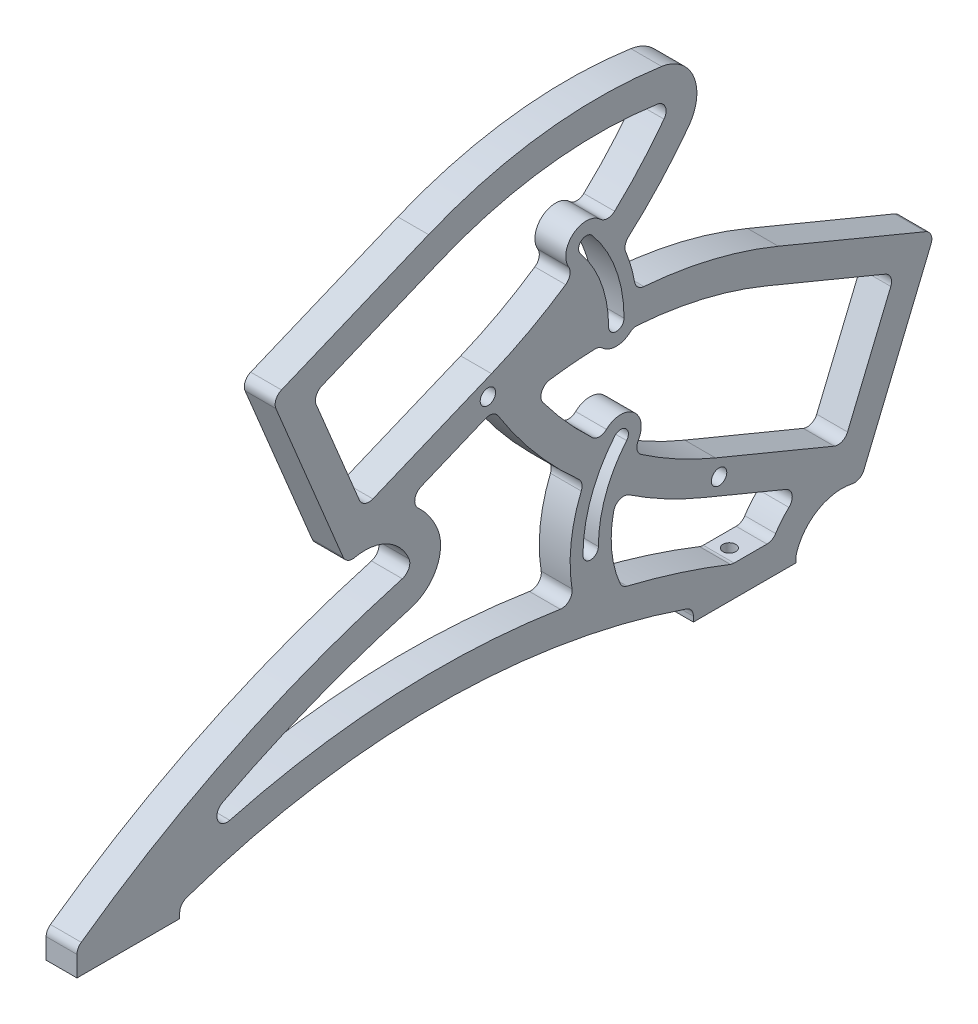
SolidWorks part; units mm, degrees
material "1060 Alloy"
ref_plane "Front Plane" through (0, 0, 0) normal (0, 0, 1) x (1, 0, 0)
ref_plane "Top Plane" through (0, 0, 0) normal (0, 1, 0) x (1, 0, 0)
ref_plane "Right Plane" through (0, 0, 0) normal (1, 0, 0) x (0, 0, -1)
sketch "Sketch1" plane through (0, 0, 0) normal (1, 0, 0) x (0, 0, -1)
  line L0 (0, 0) -> (0, 5)
  line L1 (38.8897, 78.8553) -> (54.5797, 40.9762) construction
  line L2 (38.8897, 78.8553) -> (112.8001, 109.47) construction
  line L3 (54.5797, 40.9762) -> (128.4901, 71.5909) construction
  line L4 (41.8855, 76.849) -> (54.1314, 47.2849) construction
  line L5 (112.8001, 109.47) -> (128.4901, 71.5909) construction
  line L6 (20, 1) -> (20, 0)
  line L7 (0, 0) -> (20, 0)
  line L8 (54.1314, 47.2849) -> (81.8478, 58.7654) construction
  line L9 (69.6019, 88.3295) -> (41.8855, 76.849) construction
  line L10 (80, 58) -> (105, 58) construction
  line L11 (99.1511, 74.0697) -> (80, 58) construction
  line L12 (100, 22) -> (125, 22) construction
  line L13 (125, 22) -> (105.8489, 38.0697) construction
  line L14 (166.1103, 42.8553) -> (150.4203, 4.9762) construction
  line L15 (166.1103, 42.8553) -> (92.1999, 73.47) construction
  line L16 (150.4203, 4.9762) -> (76.5099, 35.5909) construction
  line L17 (92.1999, 73.47) -> (76.5099, 35.5909) construction
  line L18 (150.8686, 11.2849) -> (163.1145, 40.849) construction
  line L19 (163.1145, 40.849) -> (135.3981, 52.3295) construction
  line L20 (123.1522, 22.7654) -> (150.8686, 11.2849) construction
  line L21 (156.9916, 26.0669) -> (84.929, 55.9162) construction
  line L22 (48.0084, 62.0669) -> (120.071, 91.9162) construction
  line L23 (152.4922, 7.3652) -> (167.0342, 42.4726)
  line L24 (167.0342, 42.4726) -> (136.5462, 55.1012)
  line L25 (68.4538, 91.1012) -> (37.9658, 78.4726)
  line L26 (37.9658, 78.4726) -> (52.5078, 43.3652)
  line L27 (63.7245, 48.0113) -> (81.1111, 55.2131)
  line L28 (140, 0) -> (140, 1)
  line L29 (152.4922, 7.3652) -> (143.6238, 11.0386) construction
  line L30 (80.6997, 61.537) -> (55.755, 51.2046)
  line L31 (55.755, 51.2046) -> (45.8052, 75.2254)
  line L32 (45.8052, 75.2254) -> (70.7499, 85.5579)
  line L33 (124.3003, 25.537) -> (149.245, 15.2046)
  line L34 (149.245, 15.2046) -> (159.1948, 39.2254)
  line L35 (159.1948, 39.2254) -> (134.2501, 49.5579)
  line L36 (56.0604, 34.7884) -> (62.7895, 37.5756) construction
  line L37 (52.5078, 43.3652) -> (58.8317, 45.9846) construction
  line L38 (122.0042, 19.9937) -> (141.2755, 12.0113)
  line L39 (135.4645, 6) -> (127.5413, 6)
  line L43 (140, 0) -> (120, 0)
  line L56 (120, 1) -> (120, 0)
  line L63 (174.6584, 98) -> (-14.1241, 98) construction
  circle A0 centre (80, 58) radius 1.5
  circle A1 centre (125, 22) radius 1.5
  arc A2 (99.1511, 74.0697) -> (105, 58) centre (80, 58) cw construction
  arc A3 (106.5, 58) -> (100.3002, 75.0339) centre (80, 58) ccw
  arc A4 (103.5, 58) -> (98.002, 73.1055) centre (80, 58) ccw
  arc A5 (103.5, 58) -> (106.5, 58) centre (105, 58) ccw
  arc A6 (100.3002, 75.0339) -> (98.002, 73.1055) centre (99.1511, 74.0697) ccw
  arc A7 (105.8489, 38.0697) -> (100, 22) centre (125, 22) ccw construction
  arc A8 (104.6998, 39.0339) -> (98.5, 22) centre (125, 22) ccw
  arc A9 (106.998, 37.1055) -> (101.5, 22) centre (125, 22) ccw
  arc A10 (106.998, 37.1055) -> (104.6998, 39.0339) centre (105.8489, 38.0697) ccw
  arc A11 (98.5, 22) -> (101.5, 22) centre (100, 22) ccw
  arc A12 (81.8478, 58.7654) -> (116.6864, 85.8633) centre (49.9981, 135.6573) ccw construction
  arc A13 (116.6864, 85.8633) -> (113.3977, 93.803) centre (112.68, 88.8548) ccw construction
  arc A14 (113.3977, 93.803) -> (69.6019, 88.3295) centre (101.4516, 11.4375) ccw construction
  arc A15 (135.3981, 52.3295) -> (91.6023, 57.803) centre (103.5484, -24.5625) ccw construction
  arc A16 (91.6023, 57.803) -> (88.3136, 49.8633) centre (92.32, 52.8548) ccw construction
  arc A17 (88.3136, 49.8633) -> (123.1522, 22.7654) centre (155.0019, 99.6573) ccw construction
  arc A18 (106.2569, 70.3115) -> (108.7873, 61.5055) centre (80, 58) cw
  arc A19 (106.2569, 70.3115) -> (119.0902, 84.0685) centre (49.9981, 135.6573) ccw
  arc A20 (119.0902, 84.0685) -> (113.8283, 96.7719) centre (112.68, 88.8548) ccw
  arc A21 (113.8283, 96.7719) -> (68.4538, 91.1012) centre (101.4516, 11.4375) ccw
  arc A23 (81.1111, 55.2131) -> (98.7431, 34.3115) centre (155.0019, 99.6573) ccw
  arc A24 (152.4922, 7.3652) -> (140.0944, 1.6073) centre (148.9396, -1.2116) ccw
  arc A25 (140.0944, 1.6073) -> (140, 1) centre (142, 1) ccw
  arc A26 (20, 1) -> (21.3514, 2.8919) centre (22, 1) cw
  arc A27 (52.5078, 43.3652) -> (64.6372, 38.341) centre (56.0604, 34.7884) cw
  arc A28 (70.7499, 85.5579) -> (112.9671, 90.8341) centre (101.4516, 11.4375) cw
  arc A29 (112.9671, 90.8341) -> (114.2826, 87.6582) centre (112.68, 88.8548) cw
  arc A30 (114.2826, 87.6582) -> (103.1061, 75.5245) centre (49.9981, 135.6573) cw
  arc A31 (103.1061, 75.5245) -> (102.2153, 76.6408) centre (80, 58) ccw
  arc A32 (102.2153, 76.6408) -> (96.0869, 71.4985) centre (99.1511, 74.0697) ccw
  arc A33 (96.0869, 71.4985) -> (96.8505, 70.5324) centre (80, 58) cw
  arc A34 (96.8505, 70.5324) -> (80.6997, 61.537) centre (49.9981, 135.6573) cw
  arc A35 (134.2501, 49.5579) -> (108.1485, 55.5328) centre (103.5484, -24.5625) ccw
  arc A36 (101.7667, 55.645) -> (92.0329, 54.8341) centre (103.5484, -24.5625) ccw
  arc A37 (92.0329, 54.8341) -> (90.7174, 51.6582) centre (92.32, 52.8548) ccw
  arc A38 (90.7174, 51.6582) -> (101.8939, 39.5245) centre (155.0019, 99.6573) ccw
  arc A39 (101.7667, 55.645) -> (108.1485, 55.5328) centre (105, 58) ccw
  arc A40 (101.8939, 39.5245) -> (102.7847, 40.6408) centre (125, 22) cw
  arc A41 (102.7847, 40.6408) -> (108.9131, 35.4985) centre (105.8489, 38.0697) cw
  arc A42 (108.1495, 34.5324) -> (124.3003, 25.537) centre (155.0019, 99.6573) ccw
  arc A43 (108.9131, 35.4985) -> (108.1495, 34.5324) centre (125, 22) ccw
  arc A44 (120, 1) -> (118.6486, 2.8919) centre (118, 1) ccw
  arc A45 (118.6486, 2.8919) -> (21.3514, 2.8919) centre (70, -139) ccw
  arc A46 (64.6372, 38.341) -> (63.3305, 35.6502) centre (62.7895, 37.5756) cw
  arc A47 (63.3305, 35.6502) -> (0, 5) centre (117.4338, -156.8929) ccw
  arc A48 (98.7431, 34.3115) -> (96.9455, 14.6553) centre (125, 22) ccw
  arc A49 (96.9455, 14.6553) -> (11.4386, 5.591) centre (70, -139) ccw
  arc A50 (11.4386, 5.591) -> (64.9536, 29.8739) centre (117.4338, -156.8929) cw
  arc A51 (63.7245, 48.0113) -> (70.1805, 40.6371) centre (56.0604, 34.7884) cw
  arc A52 (64.9536, 29.8739) -> (70.1805, 40.6371) centre (62.7895, 37.5756) ccw
  arc A53 (105.2771, 29.2117) -> (106.1445, 12.755) centre (125, 22) ccw
  arc A54 (106.1445, 12.755) -> (127.5413, 6) centre (70, -139) cw
  arc A55 (141.2755, 12.0113) -> (135.4645, 6) centre (148.9396, -1.2116) ccw
  arc A56 (136.5462, 55.1012) -> (108.7873, 61.5055) centre (103.5484, -24.5625) ccw
  arc A57 (122.0042, 19.9937) -> (105.2771, 29.2117) centre (155.0019, 99.6573) cw
  point P17 (103.4923, 66.5505)
  point P22 (101.5077, 30.5505)
  dimension "D1" = 3
  dimension "D3" = 1.5
  dimension "D8" = 5
  dimension "D11" = 22
  dimension "D12" = 80
  dimension "D14" = 22.5
  dimension "D16" = 2
  dimension "D17" = 6
  dimension "D21" = 30
  dimension "D22" = 35
  dimension "D23" = 80
  dimension "D24" = 3
  dimension "D18" = 6
  dimension "D29" = 58
  dimension "D25" = 5
  dimension "D28" = 2
  dimension "D36" = 3
  dimension "D37" = 3
  dimension "D38" = 3
  dimension "D39" = 8
  dimension "D45" = 3
  dimension "D46" = 3
  dimension "D47" = 4
  dimension "D48" = 4
  dimension "D49" = 3
  dimension "D52" = 3
  dimension "D53" = 4
  dimension "D54" = 4
  dimension "D55" = 4
  dimension "D56" = 2
  dimension "D57" = 150
  dimension "D58" = 2
  dimension "D59" = 200
  dimension "D60" = 6
  dimension "D61" = 6
  dimension "D62" = 4
  dimension "D63" = 6
  dimension "D64" = 8
  dimension "D67" = 4
  dimension "D68" = 6
  dimension "D69" = 6
  dimension "D2" = 25
  dimension "D4" = 25
  dimension "D5" = 40
  dimension "D6" = 40
  dimension "D7" = 125
  dimension "D9" = 20
  dimension "D10" = 100
  dimension "D13" = 1
  dimension "D15" = 22.5
  dimension "D19" = 30
  dimension "D20" = 30
  dimension "D26" = 3
  dimension "D27" = 2
  dimension "D30" = 3
  dimension "D31" = 3
  dimension "D32" = 98
  dimension "D33" = 3
  dimension "D34" = 3
  dimension "D35" = 3
  dimension "D41" = 3
  dimension "D42" = 3
  dimension "D43" = 3
  dimension "D44" = 3
  dimension "D50" = 3
  dimension "D51" = 3
  dimension "D65" = 6
  dimension "D66" = 3
extrude "Boss-Extrude1" add sketch "Sketch1" along normal blind 6
fillet "Fillet1" radius 2 27 edges at (3, 14.6553, -96.9455) (3, 34.3115, -98.7431) (3, 12.755, -106.1445) (3, 12.0113, -141.2755) (3, 6, -135.4645) (3, 6, -127.5413) (3, 39.5245, -101.8939) (3, 34.5324, -108.1495) (3, 15.2046, -149.245) (3, 39.2254, -159.1948) (3, 42.4726, -167.0342) (3, 7.3652, -152.4922) (3, 75.5245, -103.1061) (3, 70.5324, -96.8505) (3, 51.2046, -55.755) (3, 78.4726, -37.9658) (3, 75.2254, -45.8052) (3, 43.3652, -52.5078) (3, 48.0113, -63.7245) (3, 5.591, -11.4386) (3, 5, 0) (3, 55.5328, -108.1485) (3, 55.645, -101.7667) (3, 61.5055, -108.7873) (3, 70.3115, -106.2569) (3, 29.2117, -105.2771) (3, 55.2131, -81.1111)
hole_wizard "Tap Drill for M3 Tap1" positions "Sketch3" profile "Sketch2" hole size "M3" standard "ISO"
sketch "Sketch3" plane through (0, 0, 0) normal (0, -1, 0) x (-1, 0, 0)
  line L0 (-6, 20) -> (0, 20) construction
  line L1 (0, 0) -> (0, 20) construction
  line L2 (-6, 120) -> (0, 120) construction
  point P0 (-3, 10)
  point P2 (-3, 130)
  dimension "D1" = 10
  dimension "D2" = 3
  dimension "D3" = 10
sketch "Sketch2" plane through (3, 0, -10) normal (1, 0, 0) x (0, 0, -1)
  line L0 (0, 0) -> (0, 10.7511)
  line L1 (0, 10.7511) -> (1.25, 10)
  line L2 (1.25, 10) -> (1.25, 0)
  line L5 (1.25, 0) -> (0, 0)
  line L10 (0, 10.7511) -> (-1.25, 10) construction
  line L11 (0, -6.35) -> (0, 107.95) construction
  dimension "Hole Dia." = 2.5
  dimension "Hole Depth" = 10
  dimension "Drill Angle" = 118
equation "\"ˇ35\"=76.24"
